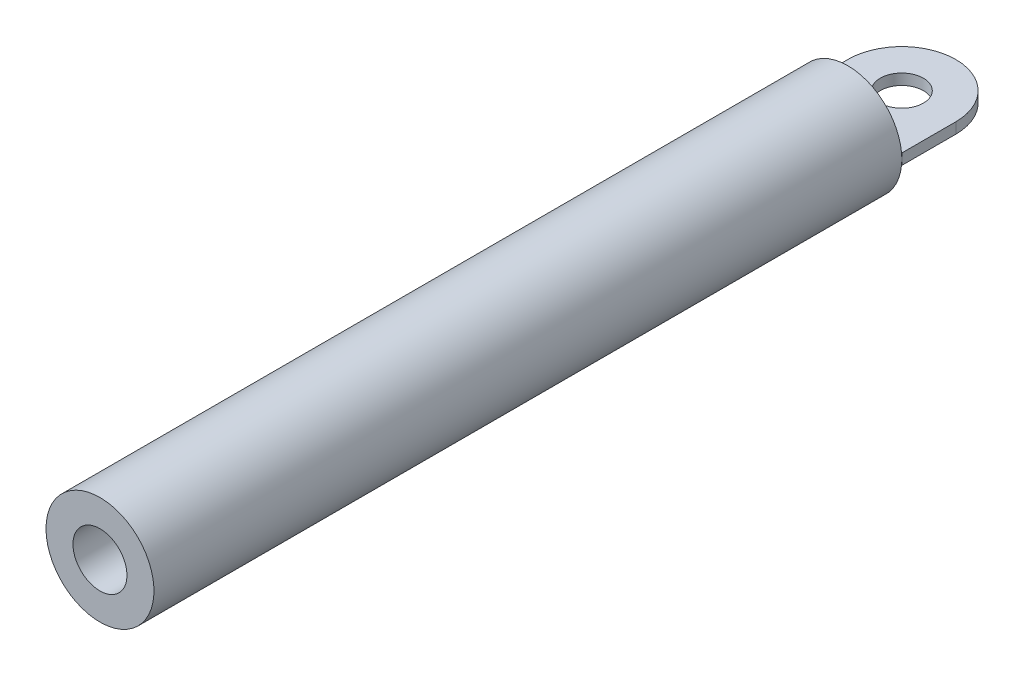
SolidWorks part; units mm, degrees
ref_plane "Front Plane" through (0, 0, 0) normal (0, 0, 1) x (1, 0, 0)
ref_plane "Top Plane" through (0, 0, 0) normal (0, 1, 0) x (1, 0, 0)
ref_plane "Right Plane" through (0, 0, 0) normal (1, 0, 0) x (0, 0, -1)
sketch "Sketch1" plane through (0, 0, 0) normal (0, 1, 0) x (1, 0, 0)
  line L0 (-1.5875, -47.1691) -> (-1.5875, -3.175)
  line L1 (-3.175, 0) -> (3.175, 0) construction
  line L2 (-3.175, 0) -> (-3.175, -47.1691)
  line L3 (-3.175, -47.1691) -> (3.175, -47.1691)
  line L4 (3.175, 0) -> (3.175, -47.1691)
  line L5 (-1.5875, -3.175) -> (1.5875, -3.175)
  line L6 (1.5875, -3.175) -> (1.5875, -47.1691)
  line L7 (-1.5875, -3.175) -> (-1.5875, 2.7496)
  line L8 (-1.5875, 2.7496) -> (1.5875, 2.7496)
  line L9 (1.5875, 2.7496) -> (1.5875, -3.175)
  line L10 (0, 0) -> (0, -50000) construction
  line L11 (0, -3.175) -> (0, 3.175)
  line L12 (0, -3.175) -> (0, -28.575)
  line L13 (-1.5875, -28.575) -> (1.5875, -28.575)
  line L14 (-1.5875, -3.175) -> (-3.175, -3.175)
  line L15 (1.5875, -3.175) -> (3.175, -3.175)
  circle A0 centre (0, 0) radius 3.175
  arc A1 (3.175, 0) -> (-3.175, 0) centre (0, 0) ccw
  circle A2 centre (0, 0) radius 1.27
  point P9 (0, -3.175)
  dimension "D1" = 43.9941
  dimension "D2" = 6.35
  dimension "D5" = 2.54
  dimension "D3" = 3.175
  dimension "D4" = 25.4
revolve "Revolve6" add sketch "Sketch1" angle 360 about L10 region at (-2.3813, 0, 25.172)
extrude "Boss-Extrude1" add sketch "Sketch1<10>" against normal blind 0.3175 and the other way blind 0.3175 contours A2 L11 L8 L7 A0 | A2 L11 A0 L9 L8 | L11 A0 L8 | L8 A0 L11 | L7 A0 | L9 A0 | A0 L9 L15 L4 | A0 L5 L9 | A0 L7 L5 | A0 L2 L14 L7 region at (-1.1961, 0, 3.049) region at (-2.6086, 0, 2.4002) region at (1.1961, 0, 3.049) region at (-0.8059, 0, 3.0076) region at (0.0613, 0, 2.2225) region at (-2.2384, 0, 0) region at (2.6086, 0, 2.4002) region at (2.2384, 0, 0) region at (-0.601, 0, -2.9208) region at (0.601, 0, -2.9208)
sketch "Sketch1<10>" plane through (0, 0, 0) normal (0, 1, 0) x (1, 0, 0) same geometry as "Sketch1"
